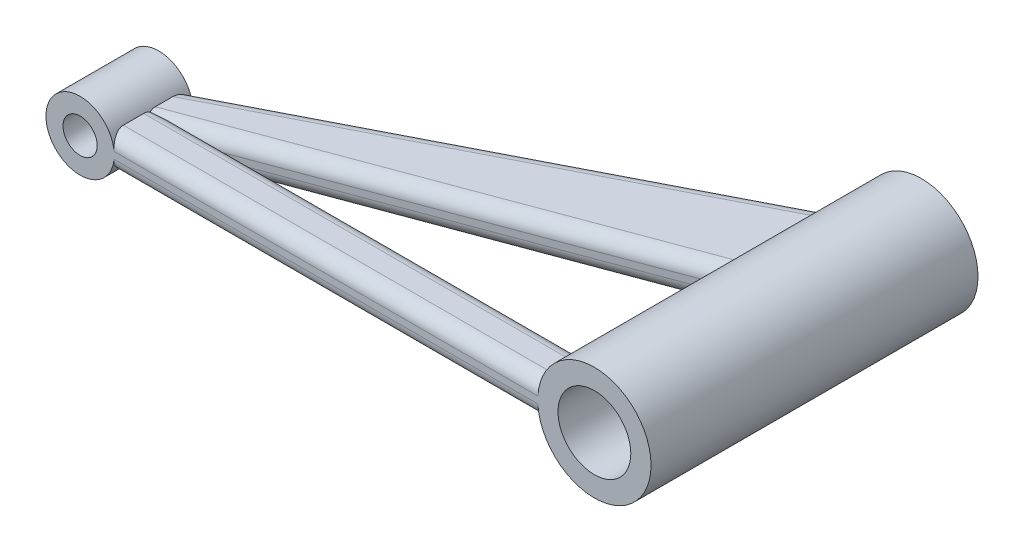
SolidWorks part; units mm, degrees
material "Thornel Mat VMA"
ref_plane "Front Plane" through (0, 0, 0) normal (0, 0, 1) x (1, 0, 0)
ref_plane "Top Plane" through (0, 0, 0) normal (0, 1, 0) x (1, 0, 0)
ref_plane "Right Plane" through (0, 0, 0) normal (1, 0, 0) x (0, 0, -1)
sketch "Sketch1" plane through (0, 0, 0) normal (0, 1, 0) x (1, 0, 0)
  line L0 (-63.9674, -18.9207) -> (86.5496, -18.9207)
  line L1 (86.5496, -18.9207) -> (86.5496, 76.7714)
  line L2 (86.5496, 76.7714) -> (-63.9674, 4.0793)
  line L3 (-63.9674, 4.0793) -> (-63.9674, -18.9207)
extrude "Boss-Extrude1" add sketch "Sketch1" along normal blind 10
sketch "Sketch2" plane through (0, 0, 18.9207) normal (0, 0, 1) x (1, 0, 0)
  line L0 (-63.9674, 10) -> (-63.9674, 0) construction
  circle A0 centre (-63.9674, 5) radius 5
  circle A1 centre (-63.9674, 5) radius 10
extrude "Boss-Extrude2" add sketch "Sketch2" against normal up to vertex (23 mm away) up to point (-63.9674, 0, -4.0793)
sketch "Sketch3" plane through (0, 0, 18.9207) normal (0, 0, 1) x (1, 0, 0)
  line L0 (-63.9674, 10) -> (-63.9674, 0) construction
  circle A0 centre (-63.9674, 5) radius 5
extrude "Cut-Extrude1" cut sketch "Sketch3" against normal blind 27
sketch "Sketch4" plane through (0, 10, 0) normal (0, 1, 0) x (1, 0, 0)
  line L0 (-63.9674, 4.0793) -> (-55.3072, 4.0793)
  line L1 (-55.3072, 4.0793) -> (86.5496, 76.7714)
  line L2 (86.5496, 76.7714) -> (-63.9674, 4.0793)
extrude "Cut-Extrude2" cut sketch "Sketch4" against normal blind 27
sketch "Sketch5" plane through (0, 0, 18.9207) normal (0, 0, 1) x (1, 0, 0)
  line L0 (86.5496, 10) -> (86.5496, 0) construction
  circle A0 centre (86.5496, 5) radius 9.5
  circle A1 centre (86.5496, 5) radius 16.5771
extrude "Boss-Extrude3" add sketch "Sketch5" against normal up to vertex (95.6921 mm away) up to point (86.5496, 10, -76.7714)
sketch "Sketch6" plane through (0, 0, 18.9207) normal (0, 0, 1) x (1, 0, 0)
  line L0 (86.5496, 10) -> (86.5496, 0) construction
  circle A0 centre (86.5496, 5) radius 10.655
  dimension "D1" = 21.31
extrude "Cut-Extrude3" cut sketch "Sketch6" against normal blind 100
sketch "Sketch7" plane through (0, 10, 0) normal (0, 1, 0) x (1, 0, 0)
  line L0 (-42.1947, -4.9673) -> (69.5637, 36.5775)
  line L3 (69.5637, 36.5775) -> (69.5637, -4.9673)
  line L4 (69.5637, -4.9673) -> (-42.1947, -4.9673)
extrude "Cut-Extrude4" cut sketch "Sketch7" against normal blind 49 and the other way blind 18
fillet "Fillet1" radius 4 8 edges at (7.7187, 0, -36.3758) (7.7187, 10, -36.3758) (13.6845, 0, -15.8051) (13.6845, 10, -15.8051) (13.6845, 0, 4.9673) (13.6845, 10, 4.9673) (7.7187, 0, 18.9207) (7.7187, 10, 18.9207)
